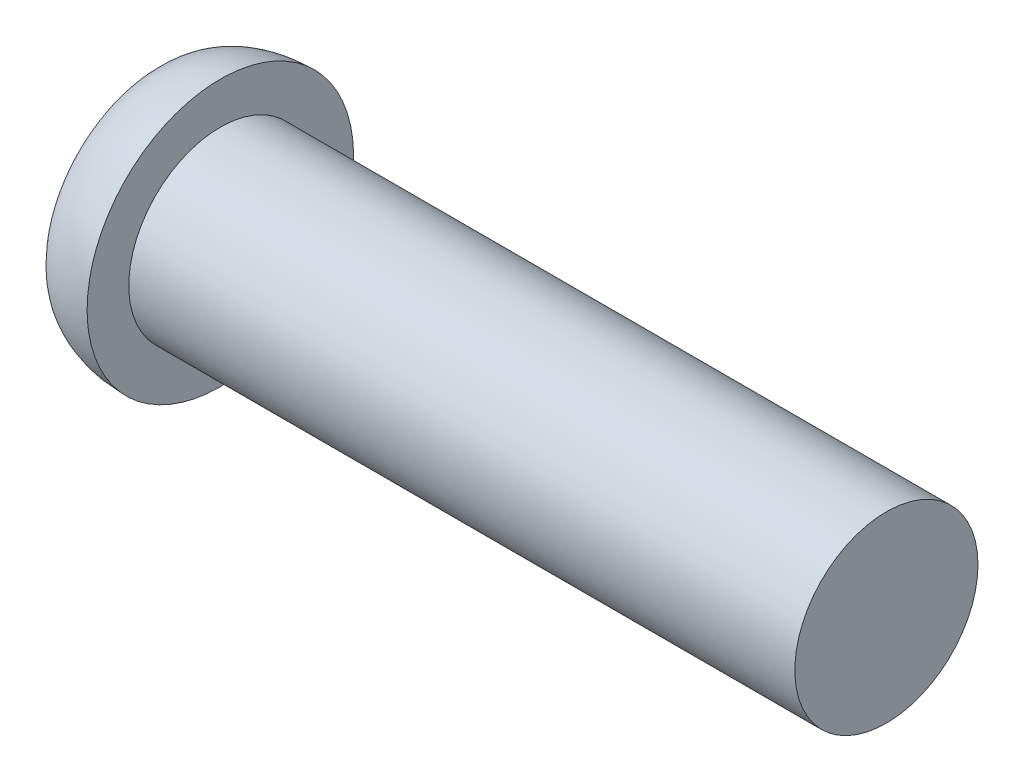
SolidWorks part; units mm, degrees
ref_plane "Front Plane" through (0, 0, 0) normal (0, 0, 1) x (1, 0, 0)
ref_plane "Top Plane" through (0, 0, 0) normal (0, 1, 0) x (1, 0, 0)
ref_plane "Right Plane" through (0, 0, 0) normal (1, 0, 0) x (0, 0, -1)
sketch "Sketch1" plane through (0, 0, 0) normal (1, 0, 0) x (0, 0, -1)
  circle A0 centre (0, 0) radius 2.75
  point P2 (0, 0)
  point P3 (0, 0)
  point P4 (0, 0)
  dimension "D1" = 5.5
extrude "Boss-Extrude1" add sketch "Sketch1" along normal blind 20
sketch "Sketch2" plane through (0, 0, 0) normal (-1, 0, 0) x (0, 0, 1)
  circle A0 centre (0, 0) radius 4
  point P2 (0, 0)
  dimension "D1" = 8
extrude "Boss-Extrude2" add sketch "Sketch2" along normal blind 2
fillet "Fillet1" radius 2 1 edges at (-2, 0, 4) second distance 1 first distance on face at (-2, 0, 4)
